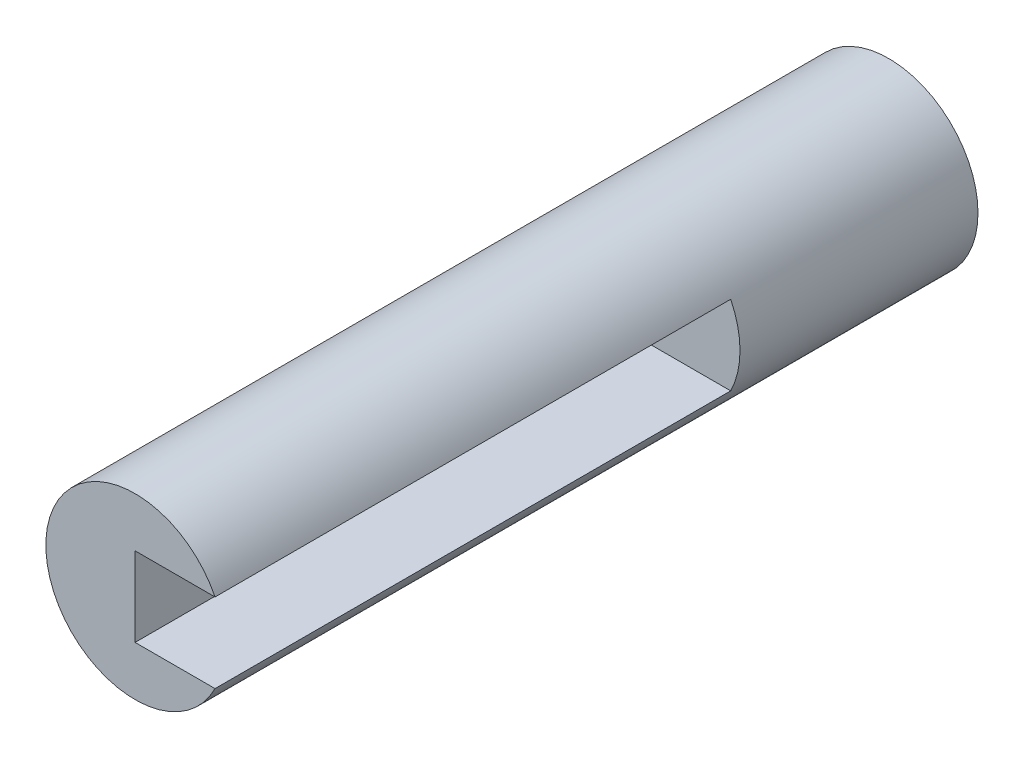
SolidWorks part; units mm, degrees
ref_plane "Front Plane" through (0, 0, 0) normal (0, 0, 1) x (1, 0, 0)
ref_plane "Top Plane" through (0, 0, 0) normal (0, 1, 0) x (1, 0, 0)
ref_plane "Right Plane" through (0, 0, 0) normal (1, 0, 0) x (0, 0, -1)
sketch "Sketch1" plane through (0, 0, 0) normal (0, 0, 1) x (1, 0, 0)
  circle A0 centre (-11.3049, 8.134) radius 4.5
  point P2 (-209.2783, -20.8175)
extrude "Boss-Extrude3" add sketch "Sketch1" along normal blind 38
sketch "Sketch3" plane through (0, 0, 0) normal (0, 0, 1) x (1, 0, 0)
  line L1 (-9.3049, 9.634) -> (-13.3049, 9.634)
  line L3 (-9.3049, 6.634) -> (-13.3049, 6.634)
  circle A0 centre (-11.3049, 8.134) radius 2.5
  circle A1 centre (-11.3049, 8.134) radius 4.5 construction
  dimension "D2" = 5
  dimension "D1" = 0
  dimension "D3" = 1.5
  dimension "D4" = 1.5
extrude "Cut-Extrude2" cut sketch "Sketch3" along normal blind 1.5 contours L1 A0 | L3 A0 region at (-11.3049, 10.0418, 0) region at (-11.3049, 6.2262, 0)
extrude "Cut-Extrude3" cut sketch "Sketch3<4>" along normal blind 7.5 contours L1 A0 L3 region at (-11.3049, 8.134, 0)
sketch "Sketch3<4>" plane through (0, 0, 0) normal (0, 0, 1) x (1, 0, 0) same geometry as "Sketch3"
ref_plane "Plane7" through (0, 0, 38) normal (0, 0, 1) x (1, 0, 0)
sketch "Sketch6" plane through (0, 0, 38) normal (0, 0, 1) x (1, 0, 0)
  line L1 (-11.3049, 10.134) -> (-3.3593, 10.134)
  line L2 (-11.3049, 10.134) -> (-11.3049, 6.134)
  line L3 (-11.3049, 6.134) -> (-3.3593, 6.134)
  line L4 (-3.3593, 10.134) -> (-3.3593, 6.134)
  circle A0 centre (-11.3049, 8.134) radius 4.5 construction
  dimension "D1" = 0
  dimension "D2" = 2
  dimension "D3" = 2
extrude "Cut-Extrude4" cut sketch "Sketch6" against normal blind 26
